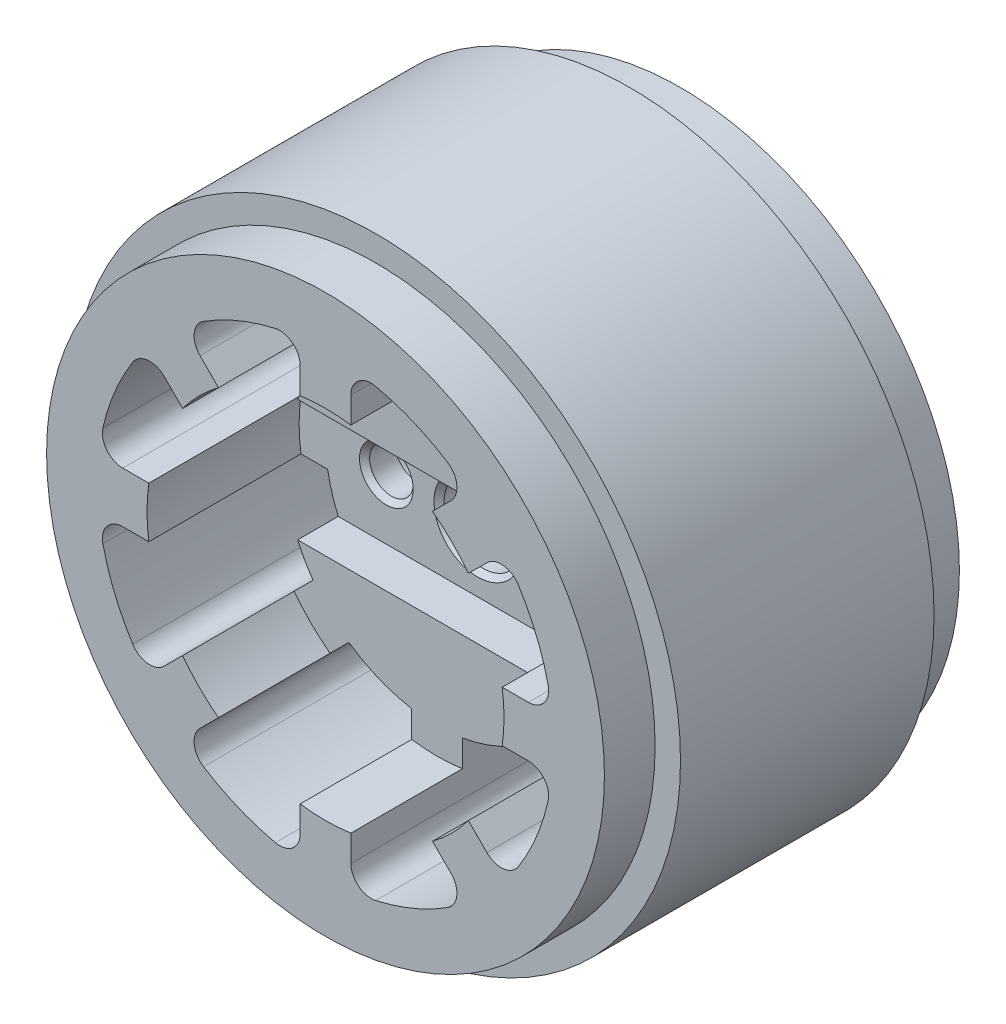
SolidWorks part; units mm, degrees
ref_plane "Front Plane" through (0, 0, 0) normal (0, 0, 1) x (1, 0, 0)
ref_plane "Top Plane" through (0, 0, 0) normal (0, 1, 0) x (1, 0, 0)
ref_plane "Right Plane" through (0, 0, 0) normal (1, 0, 0) x (0, 0, -1)
sketch "Sketch1" plane through (0, 0, 0) normal (0, 0, 1) x (1, 0, 0)
  line L0 (0, 0) -> (52.3745, 0) construction
  line L1 (0, 0) -> (0, 45.9782) construction
  line L2 (2.5, 22.3607) -> (2.5, 14.7902)
  line L3 (-13.7477, 6) -> (13.7477, 6)
  line L4 (-13.7477, -6) -> (13.7477, -6)
  line L5 (-2.5, 22.3607) -> (-2.5, 14.7902)
  line L6 (17.5792, 14.0436) -> (12.226, 8.6905)
  line L7 (14.0436, 17.5792) -> (8.6905, 12.226)
  line L8 (22.3607, -2.5) -> (14.7902, -2.5)
  line L9 (22.3607, 2.5) -> (14.7902, 2.5)
  line L10 (14.0436, -17.5792) -> (8.6905, -12.226)
  line L11 (17.5792, -14.0436) -> (12.226, -8.6905)
  line L12 (-2.5, -22.3607) -> (-2.5, -14.7902)
  line L13 (2.5, -22.3607) -> (2.5, -14.7902)
  line L14 (-17.5792, -14.0436) -> (-12.226, -8.6905)
  line L15 (-14.0436, -17.5792) -> (-8.6905, -12.226)
  line L16 (-22.3607, 2.5) -> (-14.7902, 2.5)
  line L17 (-22.3607, -2.5) -> (-14.7902, -2.5)
  line L18 (-14.0436, 17.5792) -> (-8.6905, 12.226)
  line L19 (-17.5792, 14.0436) -> (-12.226, 8.6905)
  circle A0 centre (0, 0) radius 3.8
  circle A1 centre (0, 0) radius 15
  circle A2 centre (0, 0) radius 22.5
  circle A3 centre (0, 0) radius 27.5
  circle A4 centre (9, 0) radius 3
  circle A5 centre (-9, 0) radius 3
  circle A7 centre (9, 0) radius 2.15
  circle A8 centre (-9, 0) radius 2.15
  circle A24 centre (0, 0) radius 30
  circle A25 centre (0, 0) radius 17.6
  point P16 (0, 0)
  point P17 (-17.4215, 2.5)
  point P26 (0, 0)
  point P27 (-17.4215, 2.5)
  point P29 (0, 0)
  point P87 (0, 0)
  point P138 (0, 0)
  dimension "D1" = 7.6
  dimension "D2" = 30
  dimension "D3" = 45
  dimension "D4" = 55
  dimension "D5" = 9
  dimension "D6" = 6
  dimension "D8" = 4.9391
  dimension "D9" = 4.3
  dimension "D12" = 60
  dimension "D13" = 35.2
  dimension "D14" = 7.5705
  dimension "D7" = 2.5
  dimension "D10" = 6
  dimension "D11" = 8
extrude "Boss-Extrude7" add sketch "Sketch1<15>" along normal blind 12 from offset 3 separate body contours A1
sketch "Sketch1<15>" plane through (0, 0, 0) normal (0, 0, 1) x (1, 0, 0) same geometry as "Sketch1"
extrude "Cut-Extrude2" cut sketch "Sketch1<16>" along normal blind 15 from surface contours A0 starting at face at (15, 0, 3)
sketch "Sketch1<16>" plane through (0, 0, 0) normal (0, 0, 1) x (1, 0, 0) same geometry as "Sketch1"
extrude "Cut-Extrude4" cut sketch "Sketch1<18>" along normal offset from surface (12 mm away) 3 contours A5 | A4 up to face at (3.8, 0, 15)
sketch "Sketch1<18>" plane through (0, 0, 0) normal (0, 0, 1) x (1, 0, 0) same geometry as "Sketch1"
extrude "Cut-Extrude5" cut sketch "Sketch1<19>" against normal blind 3 from surface contours A8 starting at face at (3.8, 0, 15)
sketch "Sketch1<19>" plane through (0, 0, 0) normal (0, 0, 1) x (1, 0, 0) same geometry as "Sketch1"
extrude "Cut-Extrude6" cut sketch "Sketch1" along normal up to surface (15 mm away) contours A7 up to face at (-6.85, 0, 15)
extrude "Boss-Extrude12" add sketch "Sketch1<22>" along normal blind 4 from offset 15 contours L3 A1 | L4 A1 region at (0, 9.7124, 0) region at (0, -9.7124, 0)
sketch "Sketch1<22>" plane through (0, 0, 0) normal (0, 0, 1) x (1, 0, 0) same geometry as "Sketch1"
extrude "Boss-Extrude13" add sketch "Sketch1<23>" along normal blind 30 and the other way blind 5 separate body contours A3 A2 region at (-26.7222, 0, 0)
sketch "Sketch1<23>" plane through (0, 0, 0) normal (0, 0, 1) x (1, 0, 0) same geometry as "Sketch1"
extrude "Boss-Extrude14" add sketch "Sketch1<24>" along normal up to surface (30 mm away) contours A2 | A2 | A2 | A2 | A2 | A2 | A2 | A2 region at (0, 19.997, 0) region at (14.14, 14.14, 0) region at (-14.14, 14.14, 0) region at (19.997, 0, 0) region at (-19.997, 0, 0) region at (14.14, -14.14, 0) region at (-14.14, -14.14, 0) region at (0, -19.997, 0) up to face at (22.5, 0, 30)
sketch "Sketch1<24>" plane through (0, 0, 0) normal (0, 0, 1) x (1, 0, 0) same geometry as "Sketch1"
extrude "Boss-Extrude16" add sketch "Sketch1<26>" along normal up to surface (15 mm away) and the other way up to surface from offset 5 contours L16 A25 L17 A1 | L8 A25 L9 A1 region at (16.2352, 0, 0) region at (-16.2352, 0, 0) up to face at (0, 0, 15) other way up to face at (-14.1213, 14.1213, 0)
sketch "Sketch1<26>" plane through (0, 0, 0) normal (0, 0, 1) x (1, 0, 0) same geometry as "Sketch1"
extrude "Boss-Extrude18" add sketch "Sketch1<28>" along normal blind 25 contours A24 A3 region at (-29.1515, 0, 0)
sketch "Sketch1<28>" plane through (0, 0, 0) normal (0, 0, 1) x (1, 0, 0) same geometry as "Sketch1"
extrude "Boss-Extrude19" add sketch "Sketch1<32>" along normal blind 23 and the other way blind 5 from offset 5
sketch "Sketch1<32>" plane through (0, 0, 0) normal (0, 0, 1) x (1, 0, 0) same geometry as "Sketch1"
chamfer "Chamfer5" distance 0.5 angle 45 6 edges at (-6, 0, 3) (3.8, 0, 3) (12, 0, 3) (11.15, 0, 15) (3.8, 0, 15) (-6.85, 0, 15)
fillet "Fillet1" radius 2 16 edges at (-14.0436, -17.5792, 15) (-2.5, -22.3607, 15) (2.5, -22.3607, 15) (14.0436, -17.5792, 15) (17.5792, -14.0436, 15) (22.3607, -2.5, 15) (22.3607, 2.5, 15) (17.5792, 14.0436, 15) (14.0436, 17.5792, 15) (2.5, 22.3607, 15) (-2.5, 22.3607, 15) (-14.0436, 17.5792, 15) (-17.5792, 14.0436, 15) (-22.3607, 2.5, 15) (-17.5792, -14.0436, 15) (-22.3607, -2.5, 15)
sketch "Sketch2" plane through (0, 0, 15) normal (0, 0, 1) x (1, 0, 0)
  line L6 (-13.7477, -6) -> (13.7477, -6)
  line L7 (14.7902, -2.5) -> (17.4215, -2.5)
  line L8 (14.7902, -2.5) -> (17.4215, -2.5)
  line L9 (13.7477, 6) -> (-13.7477, 6)
  line L10 (17.4215, 2.5) -> (14.7902, 2.5)
  line L11 (17.4215, 2.5) -> (14.7902, 2.5)
  line L12 (-13.7477, -6) -> (13.7477, -6)
  line L15 (13.7477, 6) -> (-13.7477, 6)
  line L18 (-14.7902, 2.5) -> (-17.4215, 2.5)
  line L19 (-14.7902, 2.5) -> (-17.4215, 2.5)
  line L20 (-17.4215, -2.5) -> (-14.7902, -2.5)
  line L21 (-17.4215, -2.5) -> (-14.7902, -2.5)
  arc A6 (13.7477, -6) -> (14.7902, -2.5) centre (0, 0) ccw
  arc A7 (17.4215, -2.5) -> (17.4215, 2.5) centre (0, 0) ccw
  arc A8 (14.7902, 2.5) -> (13.7477, 6) centre (0, 0) ccw
  arc A9 (-13.7477, 6) -> (-14.7902, 2.5) centre (0, 0) ccw
  arc A10 (-17.4215, 2.5) -> (-17.4215, -2.5) centre (0, 0) ccw
  arc A11 (-14.7902, -2.5) -> (-13.7477, -6) centre (0, 0) ccw
  arc A12 (13.7477, -6) -> (14.7902, -2.5) centre (0, 0) ccw
  arc A13 (17.4215, -2.5) -> (17.4215, 2.5) centre (0, 0) ccw
  arc A14 (14.7902, 2.5) -> (13.7477, 6) centre (0, 0) ccw
  arc A15 (-13.7477, 6) -> (-14.7902, 2.5) centre (0, 0) ccw
  arc A16 (-17.4215, 2.5) -> (-17.4215, -2.5) centre (0, 0) ccw
  arc A17 (-14.7902, -2.5) -> (-13.7477, -6) centre (0, 0) ccw
  dimension "D1" = 0
extrude "Boss-Extrude20" add sketch "Sketch1<33>" along normal up to surface (19 mm away) contours L2 A25 L5 A1 | L18 A25 L19 A1 | L14 A25 L15 A1 | L12 A25 L13 A1 | L10 A25 L11 A1 | L6 A25 L7 A1 region at (0, 16.2352, 0) region at (11.48, 11.48, 0) region at (-11.48, 11.48, 0) region at (11.48, -11.48, 0) region at (-11.48, -11.48, 0) region at (0, -16.2352, 0) up to face at (0, 10.5, 19)
sketch "Sketch1<33>" plane through (0, 0, 0) normal (0, 0, 1) x (1, 0, 0) same geometry as "Sketch1"
